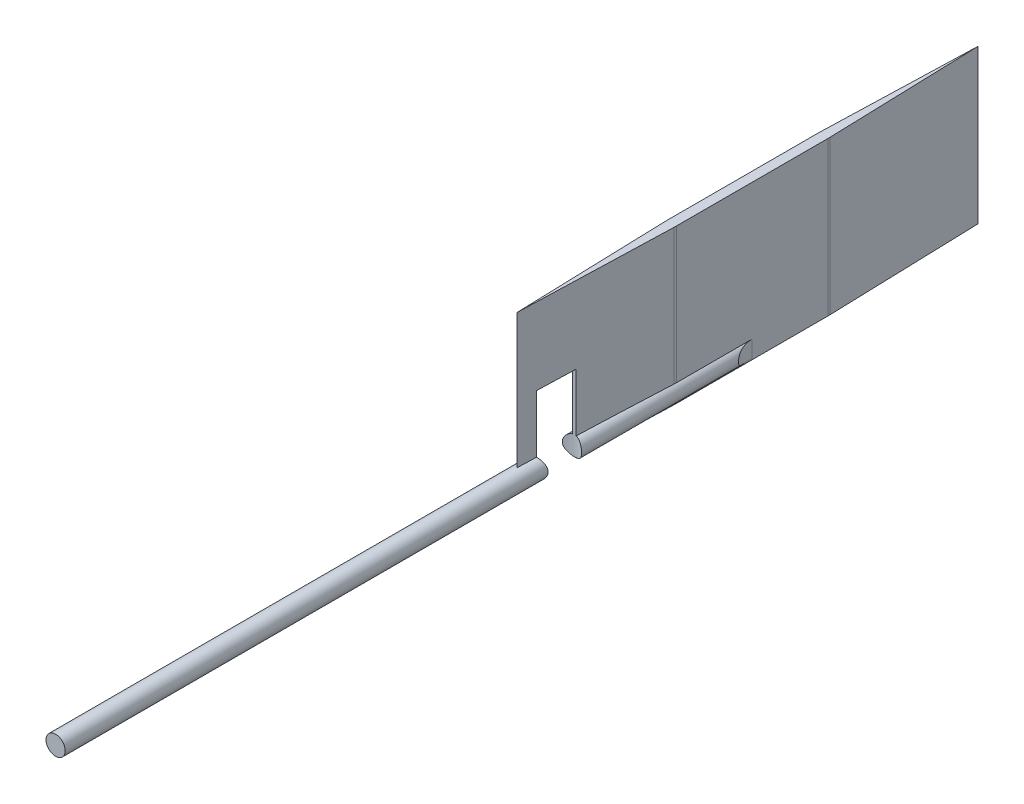
SolidWorks part; units mm, degrees
ref_plane "Front Plane" through (0, 0, 0) normal (0, 0, 1) x (1, 0, 0)
ref_plane "Top Plane" through (0, 0, 0) normal (0, 1, 0) x (1, 0, 0)
ref_plane "Right Plane" through (0, 0, 0) normal (1, 0, 0) x (0, 0, -1)
sketch "Sketch1" plane through (0, 0, 0) normal (0, 1, 0) x (1, 0, 0)
  line L0 (0, 0) -> (0, 76.2) construction
  line L1 (-0.7937, 50.8) -> (-0.7937, 25.4)
  line L2 (-0.7937, 25.4) -> (0, 0)
  line L3 (-0.7937, 50.8) -> (0, 76.2)
  line L4 (0.7937, 25.4) -> (0, 0)
  line L5 (0.7937, 50.8) -> (0, 76.2)
  line L6 (0.7937, 50.8) -> (0.7937, 25.4)
  dimension "D1" = 25.4
  dimension "D2" = 76.2
  dimension "D3" = 25.4
  dimension "D4" = 0.7937
extrude "Boss-Extrude1" add sketch "Sketch1" along normal blind 25.4
fillet "Fillet1" radius 12.7 4 edges at (-0.7937, 12.7, -25.4) (-0.7937, 12.7, -50.8) (0.7937, 12.7, -25.4) (0.7937, 12.7, -50.8)
sketch "Sketch3" plane through (0, 0, 0) normal (0, 0, 1) x (1, 0, 0)
  line L0 (0, 0) -> (0, 1.5875) construction
  circle A0 centre (0, 1.5875) radius 1.5875
  dimension "D1" = 3.175
  dimension "D2" = 1.5875
extrude "Boss-Extrude2" add sketch "Sketch3" along normal blind 76.2 and the other way blind 31.75
fillet "Fillet2" radius 6.35 2 edges at (-0.7937, 1.5875, -31.75) (0.7937, 1.5875, -31.75)
sketch "Sketch4" plane through (0, 0, 0) normal (0, 1, 0) x (1, 0, 0)
  line L0 (0, 0) -> (0, 6.35) construction
  line L1 (-3.4925, 0) -> (3.4925, 0) construction
  circle A0 centre (0, 6.35) radius 3.175
  dimension "D1" = 6.35
  dimension "D2" = 6.35
extrude "Cut-Extrude2" cut sketch "Sketch4" along normal blind 12.7
